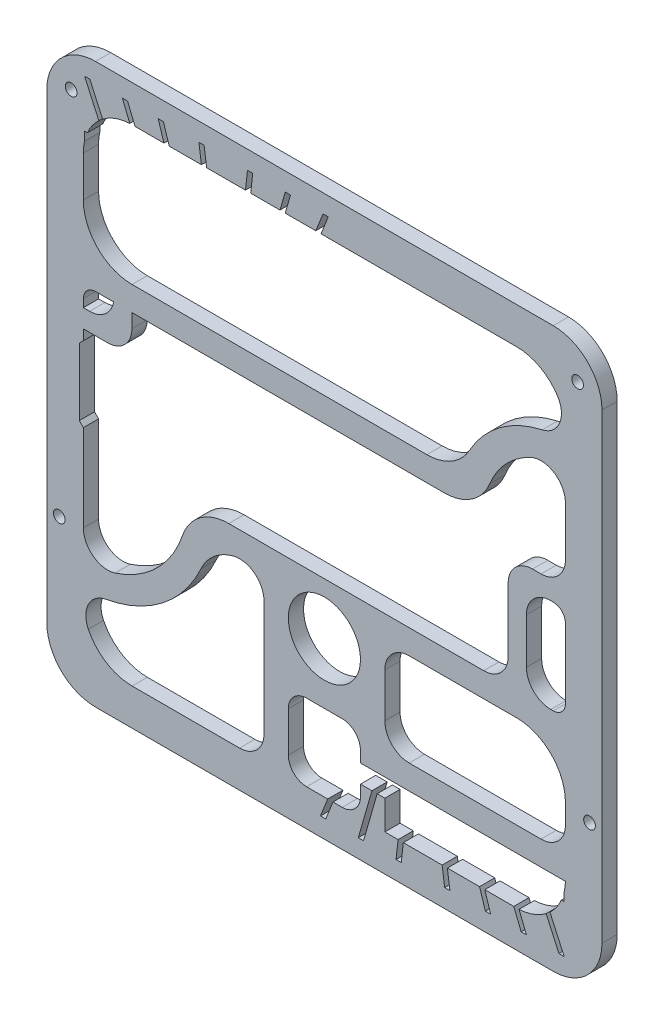
SolidWorks part; units mm, degrees
ref_plane "Front Plane" through (0, 0, 0) normal (0, 0, 1) x (1, 0, 0)
ref_plane "Top Plane" through (0, 0, 0) normal (0, 1, 0) x (1, 0, 0)
ref_plane "Right Plane" through (0, 0, 0) normal (1, 0, 0) x (0, 0, -1)
sketch "Sketch1" plane through (0, 0, 0) normal (0, 0, 1) x (1, 0, 0)
  line L0 (44.642, 21.8842) -> (44.642, 18.0742) construction
  line L1 (-8.1388, 21.8842) -> (49.7286, 21.8842)
  line L2 (-8.1388, 21.8842) -> (-8.1388, -36.406)
  line L3 (-8.1388, -36.406) -> (49.7286, -36.406)
  line L4 (49.7286, 21.8842) -> (49.7286, -36.406)
  line L5 (45.9186, -32.596) -> (-4.3288, -32.596)
  line L6 (45.9186, -32.596) -> (45.9186, 18.0742)
  line L7 (45.9186, 18.0742) -> (-4.3288, 18.0742)
  line L8 (-4.3288, -32.596) -> (-4.3288, 18.0742)
  line L9 (44.642, 19.9792) -> (-35.1587, 19.9792) construction
  line L10 (-4.3288, -31.0517) -> (-8.1388, -31.0517) construction
  line L11 (-6.2338, -31.0517) -> (-6.2338, 6.9585) construction
  line L12 (20.6521, 19.9792) -> (21.1982, 19.9792) construction
  line L13 (-6.2338, -12.887) -> (-6.2338, -25.1298) construction
  line L14 (3.0779, -32.596) -> (3.0779, -36.406) construction
  line L15 (3.0779, -34.501) -> (37.3423, -34.501) construction
  line L17 (49.7286, 15.2205) -> (45.9186, 15.2205) construction
  line L18 (47.8236, 15.2205) -> (47.8236, -0.9437) construction
  line L19 (47.8236, -1.6348) -> (47.8236, 10.608) construction
  line L20 (20.9378, -34.501) -> (20.3916, -34.501) construction
  dimension "D1" = 3.81
  dimension "D2" = 3.81
extrude "Boss-Extrude1" add sketch "Sketch1" along normal blind 1.5875
sketch "Sketch2" plane through (0, 0, 0) normal (0, 0, -1) x (-1, 0, 0)
  line L0 (-45.9186, -32.596) -> (-45.9186, 18.0742) construction
  line L1 (-34.8696, 3.653) -> (4.3288, 3.653)
  line L2 (-45.9186, 3.653) -> (-45.9186, 0.7339)
  line L3 (-37.4096, 1.113) -> (4.3288, 1.113)
  line L4 (4.3288, 3.653) -> (4.3288, 1.113)
  line L5 (4.3288, 18.0742) -> (4.3288, -32.596) construction
  line L6 (-33.4496, 1.113) -> (-36.4496, 1.113) construction
  line L7 (1.2504, -12.887) -> (-36.4496, -12.887) construction
  line L8 (-45.9186, -15.427) -> (-8.8785, -15.427)
  line L9 (-45.9186, -15.427) -> (-45.9186, -12.887)
  line L10 (-45.9186, -12.887) -> (-6.5805, -12.887)
  line L11 (1.357, -21.2563) -> (14.2432, -21.2563) construction
  line L12 (4.3288, -23.7963) -> (4.3288, -26.3363)
  line L13 (-45.9186, 12.162) -> (-45.9186, 9.622)
  arc A0 (-45.9186, 9.622) -> (-37.4096, 1.113) centre (-45.9186, 1.113) cw
  arc A1 (-45.9186, 12.162) -> (-34.8696, 3.653) centre (-45.9186, 0.7339) cw
  arc A2 (4.3288, -23.7963) -> (-6.5805, -12.887) centre (4.3288, -12.887) cw
  arc A3 (-8.8785, -15.427) -> (4.3288, -26.3363) centre (4.3288, -12.887) ccw
  circle A5 centre (1.357, -18.2591) radius 2.9972 construction
  line M5 (-45.9186, -32.596) -> (-45.9186, 18.0742)
  line M7 (4.3288, 18.0742) -> (4.3288, -32.596)
  dimension "D5" = 2.54
  dimension "D1" = 2.54
  dimension "D2" = 2.54
  dimension "D3" = 2.54
  dimension "D4" = 2.54
  dimension "D6" = 2.54
  dimension "D7" = 2.54
extrude "Boss-Extrude2" add sketch "Sketch2" against normal up to surface (1.5875 mm away) contours A1 A0 L3 L1 M5 M7 | L10 L8 M5 M7 region at (15.2704, 3.1385, 0) region at (-3.8086, -25.0663, 0) up to face at (20.7949, -7.2609, 1.5875)
sketch "Sketch3" plane through (0, 0, 0) normal (0, 0, -1) x (-1, 0, 0)
  line L0 (-45.9186, -1.1649) -> (-39.9496, -1.1649)
  line L1 (-45.9186, -12.887) -> (-45.9186, 9.622) construction
  line L2 (-39.9496, -4.387) -> (-39.9496, -11.387) construction
  line L3 (-39.9496, -1.1649) -> (-39.9496, -12.887)
  line L4 (-45.9186, -12.887) -> (-6.5805, -12.887) construction
  line L5 (-39.9496, -12.887) -> (-41.8546, -12.887)
  line L6 (-41.8546, -12.887) -> (-41.8546, -3.0699)
  line L7 (-41.8546, -3.0699) -> (-45.9186, -3.0699)
  line L8 (-45.9186, -3.0699) -> (-45.9186, -1.1649)
  line L9 (-42.9468, 0.7401) -> (-53.4831, 0.7401) construction
  line L10 (-0.7296, 1.113) -> (-0.7296, -2.887)
  line L11 (-37.4096, 1.113) -> (4.3288, 1.113) construction
  line L12 (-1.9996, -2.887) -> (1.2504, -2.887) construction
  line L13 (-0.7296, -2.887) -> (4.3288, -2.887)
  line L14 (4.3288, 1.113) -> (4.3288, -23.7963) construction
  line L15 (4.3288, -2.887) -> (4.3288, -0.982)
  line L16 (4.3288, -0.982) -> (1.1754, -0.982)
  line L17 (1.1754, -0.982) -> (1.1754, 1.113)
  line L18 (1.1754, 1.113) -> (-0.7296, 1.113)
  circle A0 centre (-42.9468, 3.7373) radius 2.9972 construction
  dimension "D1" = 1.905
  dimension "D2" = 1.905
  dimension "D3" = 1.905
  dimension "D4" = 1.905
  dimension "D5" = 1.27
  dimension "D6" = 1.905
extrude "Boss-Extrude3" add sketch "Sketch3" against normal up to surface (1.5875 mm away) up to face at (21.2778, -6.3699, 1.5875)
fillet "Fillet1" radius 5.08 4 edges at (49.7286, -36.406, 0.7937) (-8.1388, -36.406, 0.7937) (-8.1388, 21.8842, 0.7937) (49.7286, 21.8842, 0.7937)
fillet "Fillet2" radius 5.08 10 edges at (8.8785, -15.427, 0.7937) (45.9186, -15.427, 0.7937) (45.9186, -32.596, 0.7937) (-4.3288, -32.596, 0.7937) (34.8696, 3.653, 0.7937) (-4.3288, 3.653, 0.7937) (45.9186, 18.0742, 0.7937) (-4.3288, 18.0742, 0.7937) (6.5805, -12.887, 0.7937) (37.4096, 1.113, 0.7937)
fillet "Fillet3" radius 2.54 11 edges at (41.8546, -3.0699, 0.7938) (39.9496, -12.887, 0.7938) (41.8546, -12.887, 0.7938) (39.9496, -1.1649, 0.7938) (45.9186, -1.1649, 0.7938) (-1.1754, -0.982, 0.7938) (0.7296, -2.887, 0.7938) (45.9186, 9.622, 0.7937) (-4.3288, -26.3363, 0.7937) (-4.3288, -23.7963, 0.7937) (45.9186, 12.162, 0.7937)
fillet "Fillet4" radius 1.27 3 edges at (45.9186, -12.887, 0.7937) (45.9186, -3.0699, 0.7938) (-4.3288, 1.113, 0.7937)
sketch "Sketch5" plane through (0, 0, 0) normal (0, 0, -1) x (-1, 0, 0)
  line L0 (-40.8386, -15.427) -> (-12.5612, -15.427) construction
  line L1 (-27.0941, -15.427) -> (-14.4957, -15.427)
  line L2 (-27.0941, -15.427) -> (-27.0941, -32.596)
  line L3 (-27.0941, -32.596) -> (-14.4957, -32.596)
  line L4 (-14.4957, -15.427) -> (-14.4957, -32.596)
  line L5 (-0.7512, -32.596) -> (-40.8386, -32.596) construction
  line L6 (-24.5541, -18.2972) -> (-27.0941, -18.2972) construction
  line L9 (-17.0357, -18.2972) -> (-14.4957, -18.2972) construction
  circle A1 centre (-20.7949, -18.2972) radius 3.7592 construction
  dimension "D1" = 2.54
extrude "Boss-Extrude4" add sketch "Sketch5" against normal up to surface (1.5875 mm away) up to face at (-3.29, -0.0173, 1.5875)
sketch "Sketch6" plane through (0, 0, 0) normal (0, 0, -1) x (-1, 0, 0)
  circle A0 centre (-20.7949, -18.2972) radius 3.7592 construction
  circle A1 centre (-20.7949, -18.2972) radius 3.7592
extrude "Cut-Extrude2" cut sketch "Sketch6" against normal up to surface (1.5875 mm away) up to face at (6.2356, -24.4396, 1.5875)
sketch "Sketch7" plane through (0, 0, 0) normal (0, 0, -1) x (-1, 0, 0)
  line L0 (-27.0941, -15.427) -> (-27.0941, -32.596) construction
  line L1 (-24.5541, -24.5964) -> (-17.0357, -24.5964)
  line L2 (-24.5541, -24.5964) -> (-24.5541, -32.596)
  line L3 (-24.5541, -32.596) -> (-17.0357, -32.596)
  line L4 (-17.0357, -24.5964) -> (-17.0357, -32.596)
  line L5 (-14.4957, -32.596) -> (-14.4957, -15.427) construction
  line L6 (-0.7512, -32.596) -> (-14.4957, -32.596) construction
  line L7 (-20.7949, -22.0564) -> (-6.5424, -22.0564) construction
  line L8 (-20.7949, -22.0564) -> (-20.7949, -21.3452) construction
  circle A0 centre (-20.7949, -18.2972) radius 3.7592 construction
  dimension "D1" = 2.54
  dimension "D2" = 2.54
  dimension "D3" = 2.54
extrude "Cut-Extrude3" cut sketch "Sketch7" against normal up to surface (1.5875 mm away) up to face at (24.5541, -18.2972, 1.5875)
fillet "Fillet5" radius 1.905 4 edges at (24.5541, -32.596, 0.7937) (17.0357, -32.596, 0.7938) (17.0357, -24.5964, 0.7938) (24.5541, -24.5964, 0.7938)
sketch "Sketch8" plane through (0, 0, 0) normal (0, 0, -1) x (-1, 0, 0)
  line L0 (-45.9186, -27.516) -> (-45.9186, -20.507) construction
  line L1 (-45.9186, -25.103) -> (-27.0941, -25.103)
  line L2 (-45.9186, -25.103) -> (-45.9186, -27.643)
  line L3 (-45.9186, -27.643) -> (-27.0941, -27.643)
  line L4 (-27.0941, -25.103) -> (-27.0941, -27.643)
  line L5 (-27.0941, -15.427) -> (-27.0941, -32.596) construction
  line L6 (-45.7916, -27.643) -> (-20.3916, -27.643) construction
  dimension "D1" = 2.54
extrude "Boss-Extrude5" add sketch "Sketch8" against normal up to surface (1.5875 mm away) up to face at (20.7949, -28.5962, 1.5875)
fillet "Fillet6" radius 2.54 5 edges at (27.0941, -15.427, 0.7937) (14.4957, -15.427, 0.7937) (14.4957, -32.596, 0.7937) (27.0941, -25.103, 0.7937) (45.9186, -25.103, 0.7937)
sketch "Sketch4" plane through (0, 0, 0) normal (0, 0, -1) x (-1, 0, 0)
  line L0 (3.2504, -2.887) -> (4.7504, -4.387) construction
  line L1 (4.7504, -11.387) -> (3.2504, -12.887) construction
  line L2 (3.2504, -2.887) -> (4.7504, -4.387)
  line L3 (4.7504, -11.387) -> (3.2504, -12.887)
  line L4 (4.7504, -4.387) -> (4.7504, -11.387) construction
  line L5 (4.7504, -4.387) -> (4.7504, -11.387)
  line L6 (3.2504, -2.887) -> (3.2504, -12.887)
  line L32 (4.2018, 13.1212) -> (4.2018, 15.0262)
  line L33 (4.2018, 15.0262) -> (1.9539, 15.0262)
  line L34 (1.9539, 15.0262) -> (4.2018, 19.9792)
  line L35 (4.2018, 19.9792) -> (3.6556, 19.9792)
  line L36 (3.6556, 19.9792) -> (1.4078, 15.0262)
  line L37 (1.4078, 15.0262) -> (-1.7417, 15.0262)
  line L38 (-1.7417, 15.0262) -> (0.2648, 19.9792)
  line L39 (0.2648, 19.9792) -> (-0.2814, 19.9792)
  line L40 (-0.2814, 19.9792) -> (-2.2879, 15.0262)
  line L41 (-2.2879, 15.0262) -> (-5.0437, 15.0262)
  line L42 (-5.0437, 15.0262) -> (-3.469, 19.9792)
  line L43 (-3.469, 19.9792) -> (-4.0152, 19.9792)
  line L44 (-4.0152, 19.9792) -> (-5.5899, 15.0262)
  line L45 (-5.5899, 15.0262) -> (-8.3965, 15.0262)
  line L46 (-8.3965, 15.0262) -> (-7.7108, 19.9792)
  line L47 (-7.7108, 19.9792) -> (-8.257, 19.9792)
  line L48 (-8.257, 19.9792) -> (-8.9427, 15.0262)
  line L49 (-8.9427, 15.0262) -> (-12.2319, 15.0262)
  line L50 (-12.2319, 15.0262) -> (-12.7781, 19.9792)
  line L51 (-12.7781, 19.9792) -> (-13.3242, 19.9792)
  line L52 (-13.3242, 19.9792) -> (-12.7781, 15.0262)
  line L53 (-12.7781, 15.0262) -> (-15.2926, 15.0262)
  line L54 (-15.2926, 15.0262) -> (-16.7151, 19.9792)
  line L55 (-16.7151, 19.9792) -> (-17.2612, 19.9792)
  line L56 (-17.2612, 19.9792) -> (-15.8388, 15.0262)
  line L57 (-15.8388, 15.0262) -> (-18.6963, 15.0262)
  line L58 (-18.6963, 15.0262) -> (-20.6521, 19.9792)
  line L59 (-20.6521, 19.9792) -> (-21.1982, 19.9792)
  line L60 (-21.1982, 19.9792) -> (-19.2425, 15.0262)
  line L61 (-19.2425, 15.0262) -> (-21.1982, 15.0262)
  line L62 (-21.1982, 15.0262) -> (-21.1982, 13.1212)
  line L63 (-21.1982, 13.1212) -> (4.2018, 13.1212)
  line L64 (4.2018, 13.1212) -> (4.2018, 15.0262)
  line L65 (4.2018, 15.0262) -> (1.9539, 15.0262)
  line L66 (1.9539, 15.0262) -> (4.2018, 19.9792)
  line L67 (4.2018, 19.9792) -> (3.6556, 19.9792)
  line L68 (3.6556, 19.9792) -> (1.4078, 15.0262)
  line L69 (1.4078, 15.0262) -> (-1.7417, 15.0262)
  line L70 (-1.7417, 15.0262) -> (0.2648, 19.9792)
  line L71 (0.2648, 19.9792) -> (-0.2814, 19.9792)
  line L72 (-0.2814, 19.9792) -> (-2.2879, 15.0262)
  line L73 (-2.2879, 15.0262) -> (-5.0437, 15.0262)
  line L74 (-5.0437, 15.0262) -> (-3.469, 19.9792)
  line L75 (-3.469, 19.9792) -> (-4.0152, 19.9792)
  line L76 (-4.0152, 19.9792) -> (-5.5899, 15.0262)
  line L77 (-5.5899, 15.0262) -> (-8.3965, 15.0262)
  line L78 (-8.3965, 15.0262) -> (-7.7108, 19.9792)
  line L79 (-7.7108, 19.9792) -> (-8.257, 19.9792)
  line L80 (-8.257, 19.9792) -> (-8.9427, 15.0262)
  line L81 (-8.9427, 15.0262) -> (-12.2319, 15.0262)
  line L82 (-12.2319, 15.0262) -> (-12.7781, 19.9792)
  line L83 (-12.7781, 19.9792) -> (-13.3242, 19.9792)
  line L84 (-13.3242, 19.9792) -> (-12.7781, 15.0262)
  line L85 (-12.7781, 15.0262) -> (-15.2926, 15.0262)
  line L86 (-15.2926, 15.0262) -> (-16.7151, 19.9792)
  line L87 (-16.7151, 19.9792) -> (-17.2612, 19.9792)
  line L88 (-17.2612, 19.9792) -> (-15.8388, 15.0262)
  line L89 (-15.8388, 15.0262) -> (-18.6963, 15.0262)
  line L90 (-18.6963, 15.0262) -> (-20.6521, 19.9792)
  line L91 (-20.6521, 19.9792) -> (-21.1982, 19.9792)
  line L92 (-21.1982, 19.9792) -> (-19.2425, 15.0262)
  line L93 (-19.2425, 15.0262) -> (-21.1982, 15.0262)
  line L94 (-21.1982, 15.0262) -> (-21.1982, 13.1212)
  line L95 (-21.1982, 13.1212) -> (4.2018, 13.1212)
  line L96 (-45.7916, -27.643) -> (-45.7916, -29.548)
  line L97 (-45.7916, -29.548) -> (-43.5438, -29.548)
  line L98 (-43.5438, -29.548) -> (-45.7916, -34.501)
  line L99 (-45.7916, -34.501) -> (-45.2455, -34.501)
  line L100 (-45.2455, -34.501) -> (-42.9976, -29.548)
  line L101 (-42.9976, -29.548) -> (-39.8482, -29.548)
  line L102 (-39.8482, -29.548) -> (-41.8546, -34.501)
  line L103 (-41.8546, -34.501) -> (-41.3085, -34.501)
  line L104 (-41.3085, -34.501) -> (-39.302, -29.548)
  line L105 (-39.302, -29.548) -> (-36.5462, -29.548)
  line L106 (-36.5462, -29.548) -> (-38.1208, -34.501)
  line L107 (-38.1208, -34.501) -> (-37.5747, -34.501)
  line L108 (-37.5747, -34.501) -> (-36, -29.548)
  line L109 (-36, -29.548) -> (-33.1934, -29.548)
  line L110 (-33.1934, -29.548) -> (-33.879, -34.501)
  line L111 (-33.879, -34.501) -> (-33.3329, -34.501)
  line L112 (-33.3329, -34.501) -> (-32.6472, -29.548)
  line L113 (-32.6472, -29.548) -> (-29.358, -29.548)
  line L114 (-29.358, -29.548) -> (-28.8118, -34.501)
  line L115 (-28.8118, -34.501) -> (-28.2656, -34.501)
  line L116 (-28.2656, -34.501) -> (-28.8118, -29.548)
  line L117 (-28.8118, -29.548) -> (-26.2973, -29.548)
  line L118 (-26.2973, -29.548) -> (-24.8748, -34.501)
  line L119 (-24.8748, -34.501) -> (-24.3286, -34.501)
  line L120 (-24.3286, -34.501) -> (-25.7511, -29.548)
  line L121 (-25.7511, -29.548) -> (-22.8935, -29.548)
  line L122 (-22.8935, -29.548) -> (-20.9378, -34.501)
  line L123 (-20.9378, -34.501) -> (-20.3916, -34.501)
  line L124 (-20.3916, -34.501) -> (-22.3474, -29.548)
  line L125 (-22.3474, -29.548) -> (-20.3916, -29.548)
  line L126 (-20.3916, -29.548) -> (-20.3916, -27.643)
  line L127 (-20.3916, -27.643) -> (-45.7916, -27.643)
  line L128 (-45.7916, -27.643) -> (-45.7916, -29.548)
  line L129 (-45.7916, -29.548) -> (-43.5438, -29.548)
  line L130 (-43.5438, -29.548) -> (-45.7916, -34.501)
  line L131 (-45.7916, -34.501) -> (-45.2455, -34.501)
  line L132 (-45.2455, -34.501) -> (-42.9976, -29.548)
  line L133 (-42.9976, -29.548) -> (-39.8482, -29.548)
  line L134 (-39.8482, -29.548) -> (-41.8546, -34.501)
  line L135 (-41.8546, -34.501) -> (-41.3085, -34.501)
  line L136 (-41.3085, -34.501) -> (-39.302, -29.548)
  line L137 (-39.302, -29.548) -> (-36.5462, -29.548)
  line L138 (-36.5462, -29.548) -> (-38.1208, -34.501)
  line L139 (-38.1208, -34.501) -> (-37.5747, -34.501)
  line L140 (-37.5747, -34.501) -> (-36, -29.548)
  line L141 (-36, -29.548) -> (-33.1934, -29.548)
  line L142 (-33.1934, -29.548) -> (-33.879, -34.501)
  line L143 (-33.879, -34.501) -> (-33.3329, -34.501)
  line L144 (-33.3329, -34.501) -> (-32.6472, -29.548)
  line L145 (-32.6472, -29.548) -> (-29.358, -29.548)
  line L146 (-29.358, -29.548) -> (-28.8118, -34.501)
  line L147 (-28.8118, -34.501) -> (-28.2656, -34.501)
  line L148 (-28.2656, -34.501) -> (-28.8118, -29.548)
  line L149 (-28.8118, -29.548) -> (-26.2973, -29.548)
  line L150 (-26.2973, -29.548) -> (-24.8748, -34.501)
  line L151 (-24.8748, -34.501) -> (-24.3286, -34.501)
  line L152 (-24.3286, -34.501) -> (-25.7511, -29.548)
  line L153 (-25.7511, -29.548) -> (-22.8935, -29.548)
  line L154 (-22.8935, -29.548) -> (-20.9378, -34.501)
  line L155 (-20.9378, -34.501) -> (-20.3916, -34.501)
  line L156 (-20.3916, -34.501) -> (-22.3474, -29.548)
  line L157 (-22.3474, -29.548) -> (-20.3916, -29.548)
  line L158 (-20.3916, -29.548) -> (-20.3916, -27.643)
  line L159 (-20.3916, -27.643) -> (-45.7916, -27.643)
  dimension "D1" = 0
  dimension "D2" = 0
extrude "Cut-Extrude1" cut sketch "Sketch4" against normal up to surface (1.5875 mm away) up to face at (36.2546, -20.5167, 1.5875)
sketch "Sketch9" plane through (0, 0, 0) normal (0, 0, -1) x (-1, 0, 0)
  circle A0 centre (-47.1886, 18.0742) radius 0.6096 construction
  circle A1 centre (5.5988, 18.0742) radius 0.6096 construction
  circle A2 centre (6.8434, -21.0912) radius 0.6096 construction
  circle A3 centre (-48.4332, -21.0912) radius 0.6096 construction
  circle A4 centre (-47.1886, 18.0742) radius 0.6096
  circle A5 centre (5.5988, 18.0742) radius 0.6096
  circle A6 centre (6.8434, -21.0912) radius 0.6096
  circle A7 centre (-48.4332, -21.0912) radius 0.6096
extrude "Cut-Extrude4" cut sketch "Sketch9" against normal up to surface (1.5875 mm away) up to face at (18.1234, -5.3808, 1.5875)
